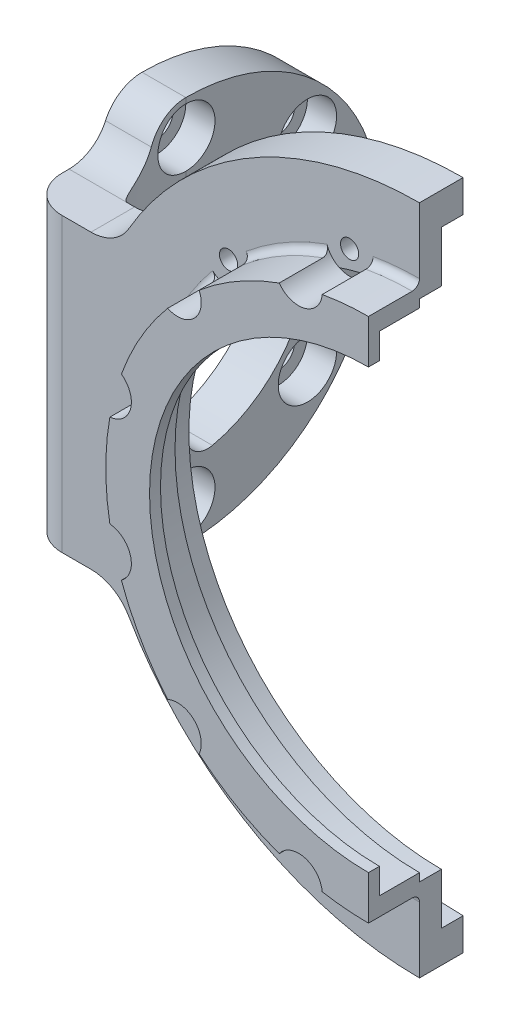
SolidWorks part; units mm, degrees
ref_plane "前视基准面" through (0, 0, 0) normal (0, 0, 1) x (1, 0, 0)
ref_plane "上视基准面" through (0, 0, 0) normal (0, 1, 0) x (1, 0, 0)
ref_plane "右视基准面" through (0, 0, 0) normal (1, 0, 0) x (0, 0, -1)
sketch "草图3" plane through (0, 0, 0) normal (0, 0, 1) x (1, 0, 0)
  circle A0 centre (0, 0) radius 34.6
  circle A1 centre (0, 0) radius 46
extrude "凸台-拉伸2" add sketch "草图3" along normal blind 3
ref_plane "基准面5" through (0, 0, 3) normal (0, 0, 1) x (1, 0, 0)
sketch "草图5" plane through (0, 0, 3) normal (0, 0, 1) x (1, 0, 0)
  circle A0 centre (0, 0) radius 33.5
  circle A1 centre (0, 0) radius 36
extrude "凸台-拉伸3" add sketch "草图5" along normal blind 5.49
sketch "草图2" plane through (0, 0, 0) normal (0, 0, 1) x (1, 0, 0)
  circle A0 centre (0, 0) radius 41.6
  circle A1 centre (0, 0) radius 46
extrude "凸台-拉伸1" add sketch "草图2" against normal blind 2.98
sketch "草图6" plane through (0, 0, 8.49) normal (0, 0, 1) x (1, 0, 0)
  circle A0 centre (0, 0) radius 30
  circle A1 centre (0, 0) radius 36
extrude "凸台-拉伸4" add sketch "草图6" along normal blind 1.5
sketch "草图8" plane through (0, 0, 0) normal (0, 0, 1) x (1, 0, 0)
  line L6 (-50, 20.008) -> (-45.0139, 20.008)
  line L8 (7.1335, 0) -> (-7.1335, 0) construction
  line L10 (-50, 20.008) -> (-50, -20.008)
  line L11 (-50, -20.008) -> (-45.0139, -20.008)
  arc A16 (-45.0139, 20.008) -> (-39.8396, 22.9958) centre (-45.0139, 25.9824) ccw
  arc A17 (-39.8396, 22.9958) -> (-39.8396, -22.9958) centre (0, 0) ccw
  arc A19 (-45.0139, -20.008) -> (-39.8396, -22.9958) centre (-45.0139, -25.9824) cw
extrude "凸台-拉伸5" add sketch "草图8" along normal blind 3 and the other way blind 2.98
hole_wizard "M3 螺纹孔的螺纹孔钻头1" positions "3D草图3" profile "草图12" hole size "M3" standard "ISO" end condition through all
sketch3d "3D草图3"
  line L2 (0, 0, 0) -> (0, 37, 0)
  line L3 (0, 0, 0) -> (11.5811, 0, 0)
  point P55 (9.5763, 35.7393, 3)
  point P76 (26.163, 26.163, 3)
  point P83 (35.7393, 9.5763, 3)
  point P96 (-35.7393, 9.5763, 3)
  point P97 (-26.163, 26.163, 3)
  point P98 (-9.5763, 35.7393, 3)
  point P99 (35.7393, -9.5763, 3)
  point P100 (26.163, -26.163, 3)
  point P101 (9.5763, -35.7393, 3)
  point P102 (-9.5763, -35.7393, 3)
  point P103 (-26.163, -26.163, 3)
  point P104 (-35.7393, -9.5763, 3)
sketch "草图12" plane through (-35.7393, -9.5763, 3) normal (1, 0, 0) x (0, -1, 0)
  line L0 (0, 0) -> (0, 5.98)
  line L1 (0, 5.98) -> (1.25, 5.98)
  line L2 (1.25, 5.98) -> (1.25, 0)
  line L5 (1.25, 0) -> (0, 0)
  line L11 (0, -6.35) -> (0, 107.95) construction
  dimension "通孔孔直径" = 2.5
  dimension "通孔孔深度" = 5.98
sketch "草图13" plane through (0, 0, 3) normal (0, 0, 1) x (1, 0, 0)
  line L0 (0, 0) -> (0, 10.9464)
  line L1 (0, 0) -> (8.3109, 0)
  circle A0 centre (-35.7393, 9.5763) radius 1.25
  circle A1 centre (-26.163, 26.163) radius 2.2
  circle A2 centre (-9.5763, 35.7393) radius 2.2
  circle A3 centre (-9.5763, -35.7393) radius 2.2
  circle A4 centre (-26.163, -26.163) radius 2.2
  circle A5 centre (-35.7393, -9.5763) radius 1.25
  circle A6 centre (9.5763, -35.7393) radius 2.2
  circle A7 centre (26.163, -26.163) radius 2.2
  circle A8 centre (9.5763, 35.7393) radius 2.2
  circle A9 centre (26.163, 26.163) radius 2.2
  circle A10 centre (35.7393, -9.5763) radius 1.25
  circle A11 centre (35.7393, 9.5763) radius 1.25
extrude "切除-拉伸1" cut sketch "草图13" along normal up to next contours A5 | A4 | A0 | A1 | A2 | A9 | A11 | A10 | A6 | A3 | A8 | A7 region at (-35.7393, 9.5763, 3) region at (-26.163, 26.163, 3) region at (-9.5763, 35.7393, 3) region at (-9.5763, -35.7393, 3) region at (-26.163, -26.163, 3) region at (-35.7393, -9.5763, 3) region at (9.5763, -35.7393, 3) region at (26.163, 26.163, 3) region at (35.7393, -9.5763, 3) region at (35.7393, 9.5763, 3)
sketch "草图25" plane through (0, 0, 3) normal (0, 0, 1) x (1, 0, 0)
  circle A0 centre (-9.5763, 35.7393) radius 3.25
  circle A1 centre (-26.163, 26.163) radius 3.25
  circle A2 centre (-35.7393, 9.5763) radius 3.25
  circle A3 centre (-35.7393, -9.5763) radius 3.25
  circle A4 centre (-26.163, -26.163) radius 3.25
  circle A5 centre (-9.5763, -35.7393) radius 3.25
extrude "切除-拉伸9" cut sketch "草图25" along normal blind 10
ref_plane "基准面6" through (-50, 0, 0) normal (-1, 0, 0) x (0, 0, 1)
sketch "草图26" plane through (-50, 0, 0) normal (-1, 0, 0) x (0, 0, 1)
  line L1 (-2.98, -20.008) -> (3, -20.008)
  line L5 (3, 20.008) -> (3, -20.008) construction
  line L6 (-2.98, 20.008) -> (3, 20.008)
  line L7 (3, 12.2277) -> (3, 23.2096) construction
  line L8 (3, 20.008) -> (3, -20.008)
  line L9 (-2.98, -20.008) -> (3, -20.008)
  arc A8 (-12.98, 26.5) -> (-12.98, -26.5) centre (-12.98, 0) ccw
  arc A9 (-12.98, 26.5) -> (-7.98, 23.254) centre (-12.98, 21.0261) cw
  arc A10 (-2.98, 20.008) -> (-7.98, 23.254) centre (-2.98, 25.4819) cw
  arc A11 (-2.98, -20.008) -> (-7.98, -23.254) centre (-2.98, -25.4819) ccw
  arc A12 (-12.98, -26.5) -> (-7.98, -23.254) centre (-12.98, -21.0261) ccw
extrude "凸台-拉伸7" add sketch "草图26" along normal blind 4 and the other way blind 2 contours A8 A12 A11 L1 L8 L6 A10 A9 region at (-50, 0, -16.9157)
sketch "草图27" plane through (0, 0, 0) normal (0, 0, 1) x (1, 0, 0)
  line L0 (0, 0) -> (0, 46)
  line L1 (0, -46) -> (0, 0)
  arc A0 (-39.8396, -22.9958) -> (-39.8396, 22.9958) centre (0, 0) ccw construction
  arc A1 (0, 46) -> (0, -46) centre (0, 0) cw
extrude "切除-拉伸10" cut sketch "草图27" against normal through all both and the other way through all
hole_wizard "M4 六角凹头盖的柱孔3" positions "3D草图5" profile "草图29" counterbore size "M4" standard "BSI" end condition up to next
sketch3d "3D草图5"
  point P0 (-48, 21.75, -12.98)
  point P4 (-48, 13.9806, -29.6415)
  point P28 (-48, -13.9806, -29.6415)
  point P29 (-48, -21.75, -12.98)
sketch "草图29" plane through (-48, 21.75, -12.98) normal (0, 1, 0) x (0, 0, -1)
  line L0 (0, 0) -> (0, 6)
  line L1 (0, 6) -> (2.25, 6)
  line L3 (2.25, 6) -> (2.25, 4)
  line L4 (2.25, 4) -> (4, 4)
  line L5 (4, 4) -> (4, 0)
  line L7 (4, 0) -> (0, 0)
  line L11 (0, -6.35) -> (0, 107.95) construction
  dimension "通孔孔直径" = 4.5
  dimension "通孔孔深度" = 6
  dimension "柱形沉头孔直径" = 8
  dimension "柱形沉头孔深度" = 4
fillet "圆角1" radius 5 1 edges at (-54, 0, 3)
sketch "草图30" plane through (-50, 0, 0) normal (-1, 0, 0) x (0, 0, 1)
  line L1 (-12.98, 17) -> (-12.98, -17)
  arc A7 (-12.98, -17) -> (-12.98, 17) centre (-12.98, 0) cw
extrude "切除-拉伸11" cut sketch "草图30" along normal blind 10 and the other way blind 10
fillet "圆角2" radius 3 2 edges at (-51, -17, -12.98) (-51, 17, -12.98)
fillet "圆角4" radius 2 1 edges at (-48, 0, -2.98) second distance 10 first distance on face at (-31.2671, 0, -2.98)
fillet "圆角5" radius 1 7 edges at (-3.1826, -35.859, 3) (-18, -31.1769, 3) (-31.1769, -18, 3) (-36, 0, 3) (-3.1826, 35.859, 3) (-18, 31.1769, 3) (-31.1769, 18, 3)
